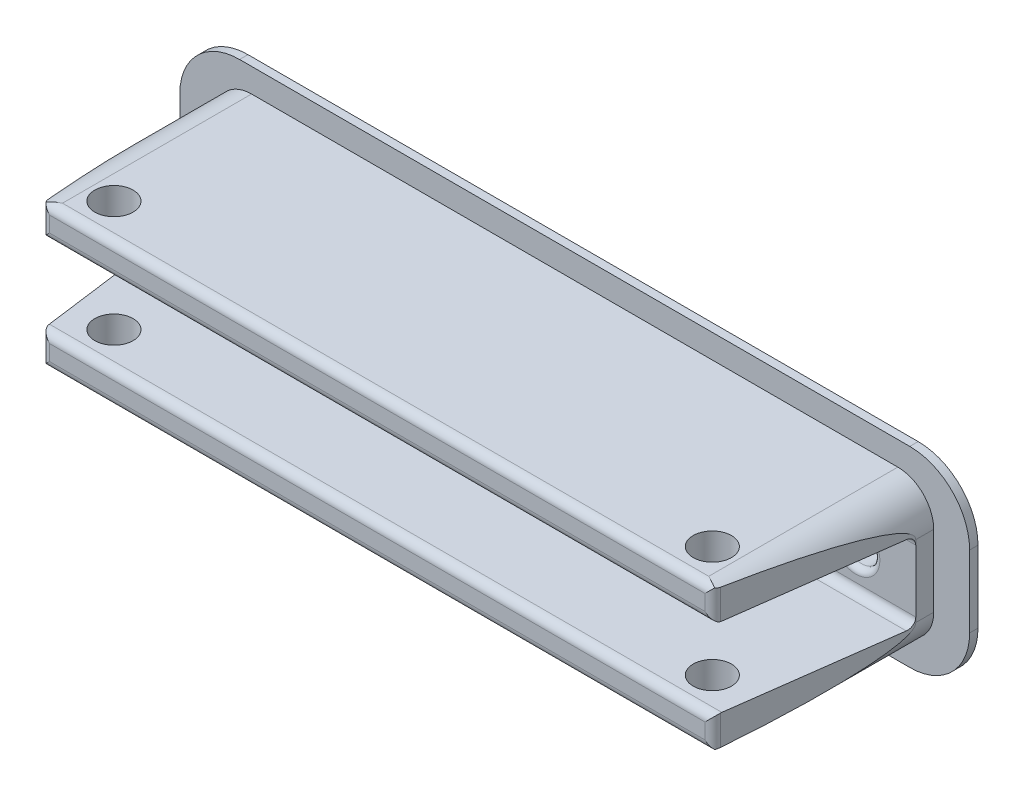
SolidWorks part; units mm, degrees
ref_plane "Front" through (0, 0, 0) normal (0, 0, 1) x (1, 0, 0)
ref_plane "Top" through (0, 0, 0) normal (0, 1, 0) x (1, 0, 0)
ref_plane "Right" through (0, 0, 0) normal (1, 0, 0) x (0, 0, -1)
sketch "Sketch1" plane through (0, 0, 0) normal (0, 0, 1) x (1, 0, 0)
  line L1 (30, -6) -> (-30, -6)
  line L2 (30, -6) -> (30, 6)
  line L3 (30, 6) -> (-30, 6)
  line L4 (-30, -6) -> (-30, 6)
  line L5 (30, -6) -> (-30, 6) construction
  line L6 (30, 6) -> (-30, -6) construction
  point P0 (0, 0)
  dimension "D1" = 60
  dimension "D2" = 12
extrude "Boss-Extrude1" add sketch "Sketch1" along normal blind 18.5
sketch "Sketch2" plane through (0, 0, 18.5) normal (0, 0, 1) x (1, 0, 0)
  line L1 (32.5, -3.3) -> (-32.5, -3.3)
  line L2 (32.5, -3.3) -> (32.5, 3.3)
  line L3 (32.5, 3.3) -> (-32.5, 3.3)
  line L4 (-32.5, -3.3) -> (-32.5, 3.3)
  line L5 (32.5, -3.3) -> (-32.5, 3.3) construction
  line L6 (32.5, 3.3) -> (-32.5, -3.3) construction
  point P0 (0, 0)
  dimension "D1" = 6.6
  dimension "D2" = 65
extrude "Cut-Extrude1" cut sketch "Sketch2" against normal blind 15
sketch "Sketch3" plane through (0, 6, 0) normal (0, 1, 0) x (1, 0, 0)
  line L0 (0, 0) -> (0, 7.6512)
  line L1 (30, -18.5) -> (-30, -18.5) construction
  circle A0 centre (-25, -15.5) radius 1.6
  circle A1 centre (25, -15.5) radius 1.6
  dimension "D3" = 3.2
  dimension "D1" = 25
  dimension "D2" = 3
extrude "Cut-Extrude2" cut sketch "Sketch3" against normal through all contours A1 | A0 region at (-25, 6, 15.5) region at (25, 6, 15.5)
sketch "Sketch4" plane through (0, -3.3, 0) normal (0, 1, 0) x (1, 0, 0)
  line L0 (-30, -3.5) -> (-28, -18.5)
  line L1 (-30, -18.5) -> (30, -18.5) construction
  line L2 (-28, -18.5) -> (-30, -18.5)
  line L3 (-30, -18.5) -> (-30, -3.5)
  dimension "D1" = 2
extrude "Cut-Extrude3" cut sketch "Sketch4" against normal through all and the other way through all
mirror "Mirror1" about plane through (0, 0, 0) normal (1, 0, 0) of "Cut-Extrude3"
fillet "Fillet1" radius 0.7 2 edges at (0, 3.3, 3.5) (0, -3.3, 3.5)
fillet "Fillet3" radius 0.7 8 edges at (-28, -4.65, 18.5) (0, -3.3, 18.5) (28, -4.65, 18.5) (0, -6, 18.5) (-28, 4.65, 18.5) (0, 6, 18.5) (28, 4.65, 18.5) (0, 3.3, 18.5)
fillet "Fillet4" radius 3 4 edges at (30, -6, 1.75) (30, 6, 1.75) (-30, 6, 1.75) (-30, -6, 1.75)
sketch "Sketch5" plane through (0, 0, 3.5) normal (0, 0, 1) x (1, 0, 0)
  line L0 (0, 0) -> (0, 11.4312)
  circle A0 centre (-25, 0) radius 1.5
  circle A1 centre (25, 0) radius 1.5
  dimension "D1" = 3
  dimension "D2" = 25
extrude "Cut-Extrude4" cut sketch "Sketch5" against normal through all contours A0 | A1 region at (-25, 0, 3.5) region at (25, 0, 3.5)
fillet "Fillet5" radius 0.5 2 edges at (26.5, 0, 3.5) (-23.5, 0, 3.5)
sketch "Sketch6" plane through (0, 0, 0) normal (0, 0, 1) x (1, 0, 0)
  line L1 (36.8734, 14.2986) -> (-36.8734, 14.2986)
  line L2 (36.8734, 14.2986) -> (36.8734, -14.2986)
  line L3 (36.8734, -14.2986) -> (-36.8734, -14.2986)
  line L4 (-36.8734, 14.2986) -> (-36.8734, -14.2986)
  line L5 (36.8734, 14.2986) -> (-36.8734, -14.2986) construction
  line L6 (36.8734, -14.2986) -> (-36.8734, 14.2986) construction
  point P0 (0, 0)
extrude "Cut-Extrude5" cut sketch "Sketch6" along normal blind 2
sketch "Sketch8" plane through (0, 0, 2) normal (0, 0, -1) x (-1, 0, 0)
  line L1 (28, -8) -> (-28, -8)
  line L2 (33, -3) -> (33, 3)
  line L3 (28, 8) -> (-28, 8)
  line L4 (-33, -3) -> (-33, 3)
  line L5 (33, -8) -> (-33, 8) construction
  line L6 (33, 8) -> (-33, -8) construction
  circle A0 centre (-25, 0) radius 1.5
  circle A1 centre (25, 0) radius 1.5
  arc A2 (33, -3) -> (28, -8) centre (28, -3) cw
  arc A3 (33, 3) -> (28, 8) centre (28, 3) ccw
  arc A4 (-33, -3) -> (-28, -8) centre (-28, -3) ccw
  arc A5 (-28, 8) -> (-33, 3) centre (-28, 3) ccw
  point P0 (0, 0)
  dimension "D3" = 5
  dimension "D1" = 66
  dimension "D2" = 16
extrude "Boss-Extrude2" add sketch "Sketch8" along normal blind 0.7
